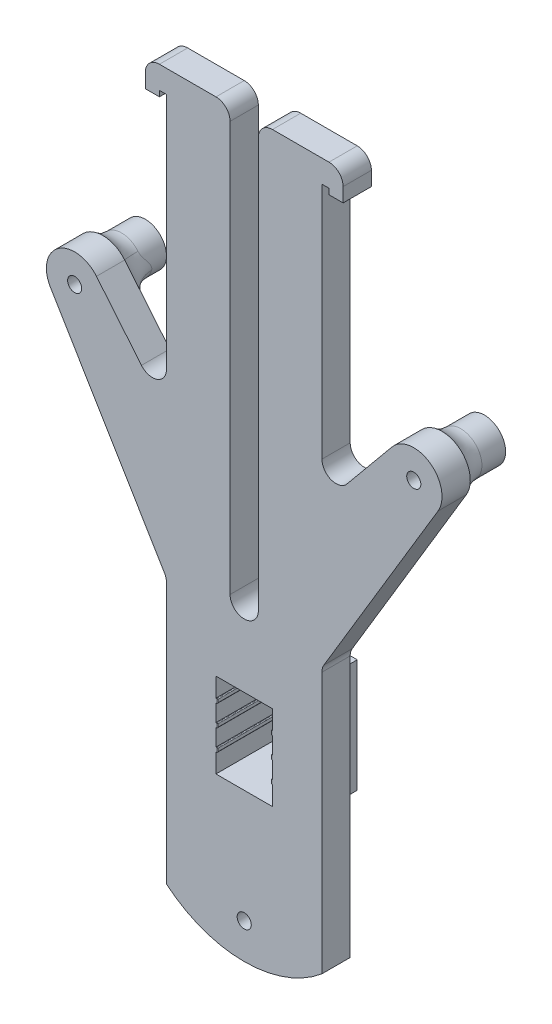
SolidWorks part; units mm, degrees
ref_plane "前视基准面" through (0, 0, 0) normal (0, 0, 1) x (1, 0, 0)
ref_plane "上视基准面" through (0, 0, 0) normal (0, 1, 0) x (1, 0, 0)
ref_plane "右视基准面" through (0, 0, 0) normal (1, 0, 0) x (0, 0, -1)
other "Configuration Table"
sketch "草图1" plane through (0, 0, 0) normal (0, 0, 1) x (1, 0, 0)
  line L1 (-5.5, 2) -> (-5.5, 50.4)
  line L2 (-5, 52) -> (-1, 52)
  line L3 (0, -1000) -> (0, 2) construction
  line L4 (5.5, 2) -> (5.5, 50.4)
  line L5 (-1, 52) -> (-1, 22)
  line L6 (1, 52) -> (1, 22)
  line L7 (1, 52) -> (5, 52)
  line L8 (0, 90) -> (0, 49000) construction
  line L9 (0, 0) -> (0, 21) construction
  line L10 (5, 52) -> (7, 52)
  line L11 (7, 52) -> (7, 50)
  line L12 (7, 50) -> (6, 50)
  line L13 (6, 50) -> (6, 50.4)
  line L14 (6, 50.4) -> (5.5, 50.4)
  line L15 (-6, 50) -> (-6, 50.4)
  line L16 (-6, 50.4) -> (-5.5, 50.4)
  line L17 (-7, 50) -> (-6, 50)
  line L18 (-7, 52) -> (-7, 50)
  line L19 (-5, 52) -> (-7, 52)
  line L20 (2, 10.5) -> (-2, 10.5)
  line L21 (-2, 10.5) -> (-2, 16.5)
  line L22 (-2, 16.5) -> (2, 16.5)
  line L23 (2, 10.5) -> (2, 16.5)
  arc A1 (-1, 22) -> (1, 22) centre (0, 22) ccw
  circle A4 centre (0, 2.5) radius 0.5
  arc A5 (-5.5, 2) -> (5.5, 2) centre (0, 8.5625) ccw
  point P8 (0, 0)
  point P9 (0, 53.7321)
  point P36 (0, 10.5)
  point P37 (0, 16.5)
  dimension "D6" = 2
  dimension "D10" = 1
  dimension "D2" = 0.5
  dimension "D3" = 2
  dimension "D4" = 2
  dimension "D5" = 30
  dimension "D7" = 1
  dimension "D8" = 2
  dimension "D9" = 0.4
  dimension "D11" = 2.5
  dimension "D12" = 2
  dimension "D13" = 6
  dimension "D14" = 14
  dimension "D15" = 4
  dimension "D16" = 50
extrude "凸台-拉伸1" add sketch "草图1" along normal blind 2
fillet "圆角1" radius 1 2 edges at (-7, 52, 1) (7, 52, 1)
fillet "圆角2" radius 1 2 edges at (-1, 52, 1) (1, 52, 1)
sketch "草图7" plane through (0, 0, 0) normal (0, 0, -1) x (-1, 0, 0)
  circle A0 centre (0, 2.5) radius 1.5
  circle A1 centre (0, 2.5) radius 0.5
  dimension "D1" = 3
  dimension "D2" = 1
extrude "凸台-拉伸3" add sketch "草图7" along normal blind 3
fillet "圆角3" radius 2 1 edges at (1.5, 2.5, 0)
sketch "草图9" plane through (0, 0, 2) normal (0, 0, 1) x (1, 0, 0)
  line L0 (-998, 13.5) -> (49002, 13.5) construction
  line L1 (2, 10.5) -> (2, 16.5) construction
  line L2 (0, -983.5) -> (0, 49016.5) construction
  line L3 (2, 16.5) -> (-2, 16.5) construction
  line L4 (10.4571, 36.7726) -> (5.5, 30.7626)
  line L5 (5.5, 2) -> (5.5, 50.4) construction
  line L6 (13.7155, 34.4719) -> (5.5, 20.7626)
  line L7 (5.5, 20.7626) -> (5.5, 30.7626)
  line L8 (-5.5, 50.4) -> (-5.5, 2) construction
  line L10 (-13.7155, 34.4719) -> (-5.5, 20.7626)
  line L11 (-10.4571, 36.7726) -> (-5.5, 30.7626)
  line L12 (-5.5, 20.7626) -> (-5.5, 30.7626)
  arc A0 (13.7155, 34.4719) -> (10.4571, 36.7726) centre (12, 35.5) ccw
  circle A1 centre (12, 35.5) radius 0.5
  arc A2 (-13.7155, 34.4719) -> (-10.4571, 36.7726) centre (-12, 35.5) cw
  circle A3 centre (-12, 35.5) radius 0.5
  circle A4 centre (0, 2.5) radius 0.5 construction
  point P5 (2, 13.5)
  point P10 (0, 16.5)
  point P26 (-5.5, 28.333)
  point P29 (-5.5, 30.8102)
  point P30 (-5.5, 30.7626)
  dimension "D3" = 4
  dimension "D6" = 1
  dimension "D1" = 33
  dimension "D2" = 12
  dimension "D4" = 10
extrude "凸台-拉伸4" add sketch "草图9" against normal blind 2
fillet "圆角5" radius 1 4 edges at (-5.5, 30.7626, 1) (-5.5, 20.7626, 1) (5.5, 20.7626, 1) (5.5, 30.7626, 1)
sketch "草图10" plane through (0, 0, 0) normal (0, 0, -1) x (-1, 0, 0)
  line L0 (-3, 17.5) -> (-3, 9.5)
  line L1 (-3, 9.5) -> (3, 9.5)
  line L2 (3, 9.5) -> (3, 17.5)
  line L3 (3, 17.5) -> (-3, 17.5)
  line L4 (2, 16.5) -> (2, 10.5) construction
  line L5 (-2, 10.5) -> (-2, 16.5) construction
  line L6 (-2, 16.5) -> (2, 16.5) construction
  line L7 (2, 10.5) -> (-2, 10.5) construction
  line L8 (-2, 16.5) -> (2, 16.5)
  line L9 (2, 16.5) -> (2, 10.5)
  line L10 (2, 10.5) -> (-2, 10.5)
  line L11 (-2, 10.5) -> (-2, 16.5)
  dimension "D1" = 1
  dimension "D2" = 1
  dimension "D3" = 1
  dimension "D4" = 1
extrude "凸台-拉伸5" add sketch "草图10" along normal blind 3
sketch "草图11" plane through (2, 0, 0) normal (-1, 0, 0) x (0, 0, 1)
  line L0 (2, 13.5) -> (-4.3403, 13.5) construction
  line L1 (2, 10.5) -> (2, 16.5) construction
  line L2 (2, 15) -> (-4.5355, 15) construction
  line L3 (2, 12) -> (-4.6484, 12) construction
  line L4 (2, 15.15) -> (2, 14.85)
  line L9 (2, 15.15) -> (-3, 15.15)
  line L10 (2, 14.85) -> (-3, 14.85)
  line L11 (-3, 15.15) -> (-3, 14.85)
  line L12 (2, 13.65) -> (2, 13.35)
  line L13 (2, 13.65) -> (-3, 13.65)
  line L14 (2, 13.35) -> (-3, 13.35)
  line L15 (-3, 13.65) -> (-3, 13.35)
  line L16 (2, 12.15) -> (2, 11.85)
  line L17 (2, 12.15) -> (-3, 12.15)
  line L18 (2, 11.85) -> (-3, 11.85)
  line L19 (-3, 12.15) -> (-3, 11.85)
  dimension "D1" = 1.5
  dimension "D2" = 1.5
  dimension "D3" = 5
  dimension "D4" = 5
  dimension "D5" = 5
  dimension "D6" = 0.3
  dimension "D7" = 0.3
  dimension "D8" = 0.3
extrude "凸台-拉伸6" add sketch "草图11" along normal blind 0.1
fillet "圆角6" radius 0.05 12 edges at (1.9, 12, 2) (1.9, 11.85, -0.5) (1.9, 12, -3) (1.9, 12.15, -0.5) (1.9, 13.5, 2) (1.9, 13.35, -0.5) (1.9, 13.5, -3) (1.9, 13.65, -0.5) (1.9, 15, 2) (1.9, 14.85, -0.5) (1.9, 15, -3) (1.9, 15.15, -0.5)
mirror "镜向1" about plane through (0, 0, 0) normal (1, 0, 0) of "圆角6", "凸台-拉伸6"
sketch "草图12" plane through (0, 0, 0) normal (0, 0, -1) x (-1, 0, 0)
  circle A0 centre (-12, 35.5) radius 1.5
  circle A1 centre (-12, 35.5) radius 0.5
  circle A3 centre (12, 35.5) radius 1.5
  circle A4 centre (12, 35.5) radius 0.5
extrude "凸台-拉伸7" add sketch "草图12" along normal blind 3
fillet "圆角9" radius 2 2 edges at (13.5, 35.5, 0) (-10.5, 35.5, 0)
fillet "圆角10" radius 2 4 edges at (3, 13.5, 0) (0, 9.5, 0) (0, 17.5, 0) (-3, 13.5, 0)
